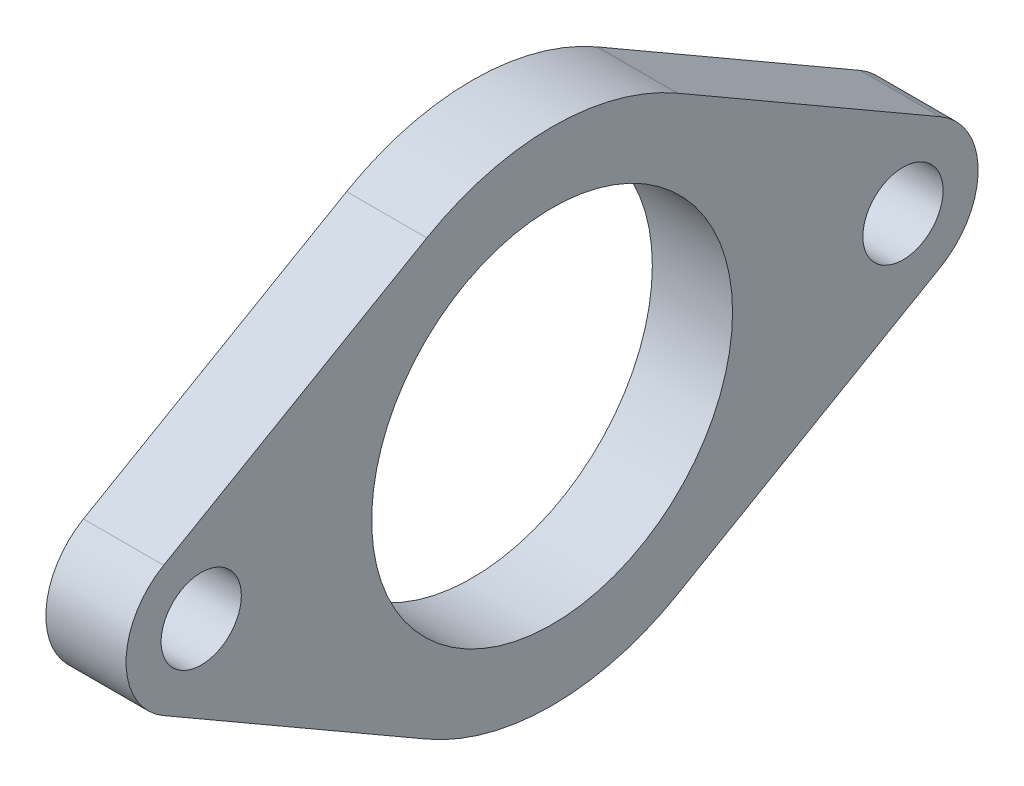
SolidWorks part; units mm, degrees
ref_plane "Front Plane" through (0, 0, 0) normal (0, 0, 1) x (1, 0, 0)
ref_plane "Top Plane" through (0, 0, 0) normal (0, 1, 0) x (1, 0, 0)
ref_plane "Right Plane" through (0, 0, 0) normal (1, 0, 0) x (0, 0, -1)
sketch "Sketch2" plane through (0, 0, 0) normal (0, 0, 1) x (1, 0, 0)
  line L0 (-11.3608, 0) -> (11.3608, 0) construction
  line L1 (0, -11.6498) -> (0, 11.6498) construction
sketch "Sketch1" plane through (0, 0, 0) normal (1, 0, 0) x (0, 0, -1)
  line L0 (-35, 0) -> (35, 0) construction
  line L1 (-12.5, -21.6506) -> (-38.75, -6.4952)
  line L2 (12.5, -21.6506) -> (38.75, -6.4952)
  line L3 (-38.75, 6.4952) -> (-12.5, 21.6506)
  line L4 (12.5, 21.6506) -> (38.75, 6.4952)
  circle A0 centre (0, 0) radius 18
  circle A1 centre (0, 0) radius 25
  circle A2 centre (-35, 0) radius 7.5
  circle A3 centre (35, 0) radius 7.5
  circle A4 centre (-35, 0) radius 4
  circle A5 centre (35, 0) radius 4
  point P8 (0, 0)
  dimension "D1" = 36
  dimension "D2" = 15
  dimension "D4" = 50
  dimension "D5" = 8
  dimension "D3" = 70
extrude "Boss-Extrude1" add sketch "Sketch1" along normal blind 4 and the other way blind 4 contours A4 A2 | A2 L0 A1 L3 | L0 A2 L1 A1 | L0 A1 A0 | A1 L0 A0 | A1 L0 A3 L4 | L0 A1 L2 A3 | A3 A5 | A0 L0 | A0 region at (0, -6.3115, 31.3561) region at (0, 9.2641, 26.4713) region at (0, -9.2641, 26.4713) region at (0, 12.2205, 21.1665) region at (0, -0.559, 21.5) region at (0, 7.6394, 0) region at (0, 9.2641, -26.4713) region at (0, -9.2641, -26.4713) region at (0, 3.6439, -41.3115)
extrude "Cut-Extrude1" cut sketch "Sketch1<3>" against normal through all and the other way through all contours L0 A0 | A0 L0 region at (0, 7.6394, 0) region at (0, -7.6394, 0)
sketch "Sketch1<3>" plane through (0, 0, 0) normal (1, 0, 0) x (0, 0, -1) same geometry as "Sketch1"
